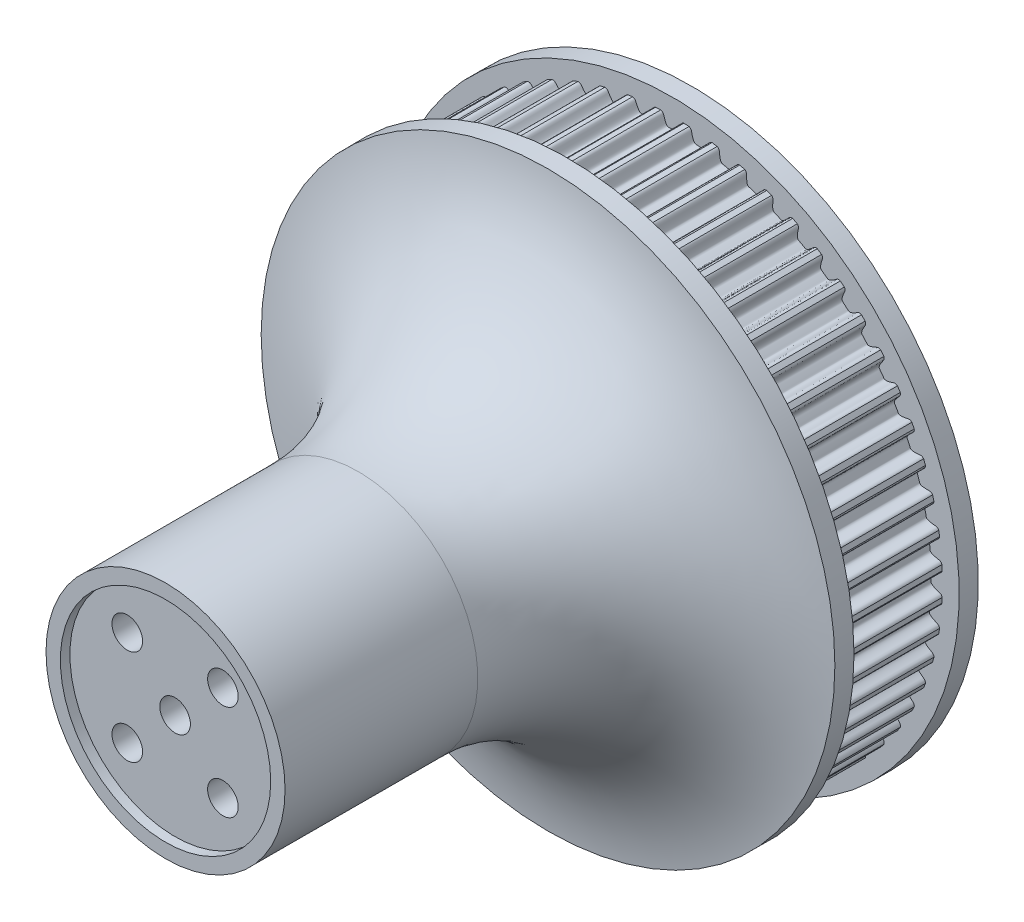
SolidWorks part; units mm, degrees
ref_plane "前视基准面" through (0, 0, 0) normal (0, 0, 1) x (1, 0, 0)
ref_plane "上视基准面" through (0, 0, 0) normal (0, 1, 0) x (1, 0, 0)
ref_plane "右视基准面" through (0, 0, 0) normal (1, 0, 0) x (0, 0, -1)
other "Configuration Table"
ref_axis "基准轴1" through (0, 0, 55) along (0, 0, -1)
sketch "SketchRevolveGearBelt01" plane through (0, 0, 0) normal (1, 0, 0) x (0, 0, -1)
  line L0 (0, 0) -> (1, 0) construction
  line L1 (9.774, 0) -> (9.774, 26.2479)
  line L2 (9.774, 26.2479) -> (9.012, 26.2479)
  line L3 (9.012, 26.2479) -> (9.012, 28.4963)
  line L4 (9.012, 28.4963) -> (9.48, 29.6263)
  line L5 (9.48, 29.6263) -> (8.7761, 29.9179)
  line L6 (8.7761, 29.9179) -> (8.25, 28.6479)
  line L7 (8.25, 28.6479) -> (8.25, 28.2529)
  line L8 (8.25, 28.2529) -> (-8.25, 28.2529)
  line L9 (-8.25, 28.2529) -> (-8.25, 28.6479)
  line L10 (-8.25, 28.6479) -> (-8.7761, 29.9179)
  line L11 (-8.7761, 29.9179) -> (-9.48, 29.6263)
  line L12 (-9.48, 29.6263) -> (-9.012, 28.4963)
  line L13 (-9.012, 28.4963) -> (-9.012, 26.2479)
  line L14 (-9.012, 26.2479) -> (-9.774, 26.2479)
  line L15 (-9.774, 26.2479) -> (-9.774, 0)
  line L16 (-9.774, 0) -> (9.774, 0)
  dimension "GearBeltFlange1OutsideLength" = 2.2484
  dimension "GearBeltFlange1X" = 0.468
  dimension "GearBeltFlange1Y" = 1.13
  dimension "GearBeltFlangeThickness" = 0.762
  dimension "GearBeltFlangeInside" = 0.395
  dimension "GearBeltOutsideDiameter" = 28.2529
  dimension "GearBeltFlange2X" = 0.468
revolve "Gates_PowerGrip_GT_3mm, 15mm Belt Width" add sketch "SketchRevolveGearBelt01" angle 360 about L0
sketch "SketchToothGearBelt01" plane through (0, 0, 0) normal (0, 0, 1) x (1, 0, 0)
  arc A0 (28.2367, 1.2911) -> (28.2367, -1.2911) centre (0, 0) cw
  spline S0 degree 3 poles (28.2367, -1.2911) (28.2364, -1.2655) (28.2322, -1.227) (28.2194, -1.1773) (28.2062, -1.141) (28.1896, -1.1062) (28.1697, -1.0732) (28.1468, -1.0422) (28.121, -1.0136) (28.0925, -0.9876) (28.0617, -0.9645) (28.0288, -0.9444) (27.9942, -0.9274) (27.9308, -0.905) (27.8508, -0.8809) (27.7571, -0.8512) (27.6784, -0.8247) (27.6045, -0.7983) (27.5353, -0.7718) (27.4709, -0.7454) (27.4113, -0.7189) (27.3564, -0.6925) (27.3063, -0.666) (27.2609, -0.6396) (27.2202, -0.6131) (27.1843, -0.5867) (27.1532, -0.5602) (27.1268, -0.5337) (27.1051, -0.5071) (27.0881, -0.4805) (27.0759, -0.4538) (27.0684, -0.4269) (27.0651, -0.3755) (27.0699, -0.3) (27.0701, -0.2) (27.0712, -0.1) (27.0714, 0) (27.0712, 0.1) (27.0701, 0.2) (27.0699, 0.3) (27.0651, 0.3755) (27.0684, 0.4269) (27.0759, 0.4538) (27.0881, 0.4805) (27.1051, 0.5071) (27.1268, 0.5337) (27.1532, 0.5602) (27.1843, 0.5867) (27.2202, 0.6131) (27.2609, 0.6396) (27.3063, 0.666) (27.3564, 0.6925) (27.4113, 0.7189) (27.4709, 0.7454) (27.5353, 0.7718) (27.6045, 0.7983) (27.6784, 0.8247) (27.7571, 0.8512) (27.8508, 0.8809) (27.9308, 0.905) (27.9942, 0.9274) (28.0288, 0.9444) (28.0617, 0.9645) (28.0925, 0.9876) (28.121, 1.0136) (28.1468, 1.0422) (28.1697, 1.0732) (28.1896, 1.1062) (28.2062, 1.141) (28.2194, 1.1773) (28.2322, 1.227) (28.2364, 1.2655) (28.2367, 1.2911) knots 0 0 0 0 0.019513 0.029269 0.039026 0.048782 0.058538 0.068295 0.078051 0.087808 0.097564 0.10732 0.117077 0.126833 0.158411 0.180602 0.201644 0.221544 0.240311 0.257955 0.274488 0.289925 0.304283 0.317585 0.32986 0.341142 0.351478 0.360929 0.369573 0.377512 0.384878 0.391837 0.398582 0.423956 0.449304 0.474652 0.5 0.525348 0.550696 0.576044 0.601418 0.608163 0.615122 0.622488 0.630427 0.639071 0.648522 0.658858 0.67014 0.682415 0.695717 0.710075 0.725512 0.742045 0.759689 0.778456 0.798356 0.819398 0.841589 0.873167 0.882923 0.89268 0.902436 0.912192 0.921949 0.931705 0.941462 0.951218 0.960974 0.970731 0.980487 1 1 1 1
extrude "ToothExtrudeCutGearBelt01" cut sketch "SketchToothGearBelt01" against normal blind 8.25 and the other way blind 8.25
pattern_circular "Tooth Pattern, 60" count 60 every 6 about axis through (0, 0, 55) along (0, 0, -1) of "ToothExtrudeCutGearBelt01"
sketch "BoreRevolveSketch" plane through (0, 0, 0) normal (1, 0, 0) x (0, 0, -1)
  line L0 (0, 0) -> (1, 0) construction
  line L1 (-9.774, 0) -> (9.774, 0)
  line L2 (9.774, 0) -> (9.774, 5)
  line L3 (9.774, 5) -> (-9.774, 5)
  line L4 (-9.774, 5) -> (-9.774, 0)
  dimension "TaperSide1" = 5
  dimension "TaperSide2" = 5
revolve "BoreRevolveCut" cut sketch "BoreRevolveSketch" angle 360 about L0
sketch "AuxiliarySketchGearBelt01" plane through (0, 0, 0) normal (0, 0, 1) x (1, 0, 0)
  circle A0 centre (0, 0) radius 28.6479 construction
  dimension "PitchDiameter" = 57.2958
sketch "草图5" plane through (0, 0, 9.774) normal (0, 0, 1) x (1, 0, 0)
  circle A0 centre (0, 0) radius 34.4314
  dimension "D1" = 68.8628
extrude "切除-拉伸2" cut sketch "草图5" against normal blind 4.55
sketch "草图6" plane through (0, 0, -9.774) normal (0, 0, -1) x (-1, 0, 0)
  circle A0 centre (0, 0) radius 32.2126
extrude "切除-拉伸3" cut sketch "草图6" against normal blind 4
sketch "草图7" plane through (0, 0, 5.224) normal (0, 0, 1) x (1, 0, 0)
  circle A0 centre (0, 0) radius 30
  dimension "D1" = 60
extrude "凸台-拉伸2" add sketch "草图7" along normal blind 2
sketch "草图8" plane through (0, 0, -5.774) normal (0, 0, -1) x (-1, 0, 0)
  circle A0 centre (0, 0) radius 30
extrude "凸台-拉伸3" add sketch "草图8" along normal blind 2
sketch "草图9" plane through (0, 0, 7.224) normal (0, 0, 1) x (1, 0, 0)
  circle A0 centre (0, 0) radius 19.1441
extrude "凸台-拉伸4" add sketch "草图9" against normal blind 14
sketch "草图10" plane through (0, 0, 7.224) normal (0, 0, 1) x (1, 0, 0)
  circle A0 centre (0, 0) radius 12.5
  dimension "D1" = 25
extrude "凸台-拉伸6" add sketch "草图10" along normal blind 20
sketch "草图12" plane through (0, 0, 27.224) normal (0, 0, 1) x (1, 0, 0)
  line L5 (-5, -5) -> (5, 5) construction
  line L6 (-5, 5) -> (5, -5) construction
  circle A0 centre (0, 0) radius 1.6
  circle A1 centre (-5, 5) radius 1.6
  circle A3 centre (5, 5) radius 1.6
  circle A4 centre (5, -5) radius 1.6
  circle A5 centre (-5, -5) radius 1.6
  point P17 (0, 0)
  dimension "D1" = 3.2
  dimension "D4" = 3.2
  dimension "D2" = 10
  dimension "D3" = 10
  dimension "D5" = 4
extrude "切除-拉伸4" cut sketch "草图12" against normal through all
sketch "草图13" plane through (0, 0, 27.224) normal (0, 0, 1) x (1, 0, 0)
  circle A0 centre (0, 0) radius 11
  dimension "D1" = 22
extrude "切除-拉伸5" cut sketch "草图13" against normal blind 1
sketch "草图14" plane through (0, 0, -7.774) normal (0, 0, -1) x (-1, 0, 0)
  circle A0 centre (15.7845, 14.8189) radius 1.9
  circle A1 centre (1.7845, 14.8189) radius 1.9
  circle A2 centre (-12.2155, 14.8189) radius 1.9
  circle A3 centre (-5.2655, -15.4311) radius 1.9
  circle A4 centre (8.7345, -15.4311) radius 1.9
  dimension "D1" = 3.8
  dimension "D2" = 3.8
  dimension "D3" = 3.8
  dimension "D4" = 3.8
  dimension "D5" = 3.8
extrude "切除-拉伸6" cut sketch "草图14" against normal up to next
sketch "草图15" plane through (0, 0, -7.774) normal (0, 0, -1) x (-1, 0, 0)
  circle A0 centre (0, 0) radius 3.5
  circle A1 centre (-5, 5) radius 3
  circle A2 centre (5, 5) radius 3
  circle A3 centre (5, -5) radius 3
  circle A4 centre (-5, -5) radius 3
  point P15 (0, 0)
  dimension "D1" = 7
  dimension "D2" = 6
  dimension "D3" = 4
extrude "切除-拉伸7" cut sketch "草图15" against normal blind 20
sketch "草图21" plane through (0, 0, 26.224) normal (0, 0, 1) x (1, 0, 0)
  circle A0 centre (0, 0) radius 12.5
  circle A1 centre (0, 0) radius 1.6
  circle A2 centre (5, -5) radius 1.6
  circle A3 centre (-5, -5) radius 1.6
  circle A4 centre (-5, 5) radius 1.6
  circle A5 centre (5, 5) radius 1.6
extrude "凸台-拉伸9" add sketch "草图21" along normal blind 9
sketch "草图22" plane through (0, 0, 35.224) normal (0, 0, 1) x (1, 0, 0)
  circle A0 centre (0, 0) radius 12.5
  circle A1 centre (-5, 5) radius 1.6
  circle A2 centre (0, 0) radius 1.6
  circle A3 centre (5, 5) radius 1.6
  circle A4 centre (5, -5) radius 1.6
  circle A5 centre (-5, -5) radius 1.6
extrude "凸台-拉伸10" add sketch "草图22" along normal blind 12
sketch "草图23" plane through (0, 0, 12.226) normal (0, 0, -1) x (-1, 0, 0)
  circle A0 centre (-5, 5) radius 3
  circle A1 centre (0, 0) radius 3.5
  circle A2 centre (5, 5) radius 3
  circle A3 centre (5, -5) radius 3
  circle A4 centre (-5, -5) radius 3
extrude "切除-拉伸13" cut sketch "草图23" against normal blind 10
sketch "草图24" plane through (0, 0, 7.224) normal (0, 0, 1) x (1, 0, 0)
  circle A0 centre (-15.7845, 14.8189) radius 1.9
  circle A1 centre (-1.7845, 14.8189) radius 1.9
  circle A2 centre (12.2155, 14.8189) radius 1.9
  circle A3 centre (-8.7345, -15.4311) radius 1.9
  circle A4 centre (5.2655, -15.4311) radius 1.9
extrude "凸台-拉伸11" add sketch "草图24" against normal blind 2
fillet "圆角6" radius 20 1 edges at (12.5, 0, 7.224)
sketch "草图25" plane through (0, 0, 47.224) normal (0, 0, 1) x (1, 0, 0)
  circle A0 centre (0, 0) radius 11
  dimension "D1" = 22
extrude "切除-拉伸14" cut sketch "草图25" against normal blind 1
